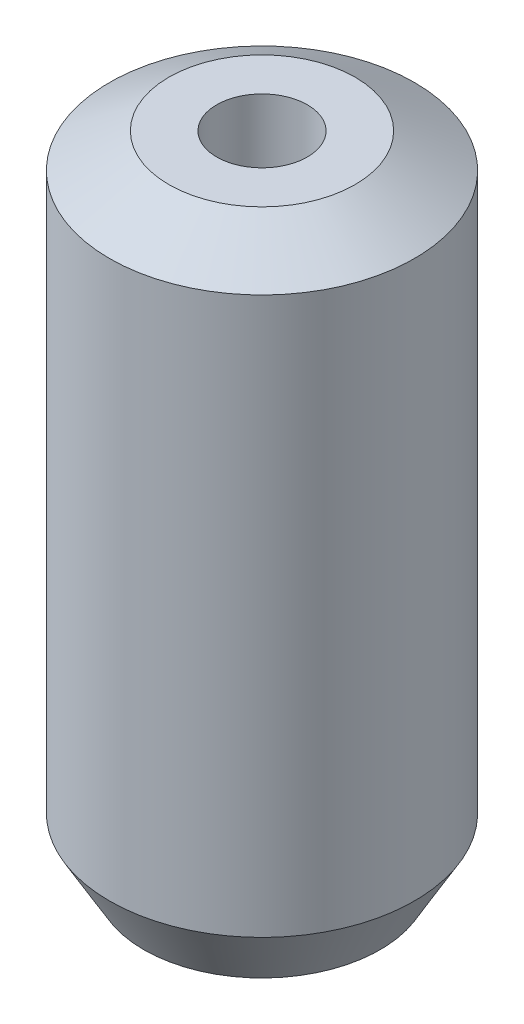
SolidWorks part; units mm, degrees
ref_plane "Front Plane" through (0, 0, 0) normal (0, 0, 1) x (1, 0, 0)
ref_plane "Top Plane" through (0, 0, 0) normal (0, 1, 0) x (1, 0, 0)
ref_plane "Right Plane" through (0, 0, 0) normal (1, 0, 0) x (0, 0, -1)
sketch "Sketch1" plane through (0, 0, 0) normal (0, 1, 0) x (1, 0, 0)
  circle A0 centre (0, 0) radius 12.5
  dimension "SHAFT_OD" = 25
extrude "Boss-Extrude1" add sketch "Sketch1" along normal blind 53.2853
sketch "Sketch2" plane through (0, 0, 0) normal (0, 1, 0) x (1, 0, 0)
  circle A0 centre (0, 0) radius 3.7147
  dimension "BORE_D" = 7.4294
extrude "Cut-Extrude1" cut sketch "Sketch2" along normal through all
chamfer "Chamfer1" distance 2.811 angle 60 2 edges at (0, 53.2853, 12.5) (0, 0, 12.5) first distance on face at (0, 53.2853, 12.5) first distance on face at (0, 0, 3.7147)
